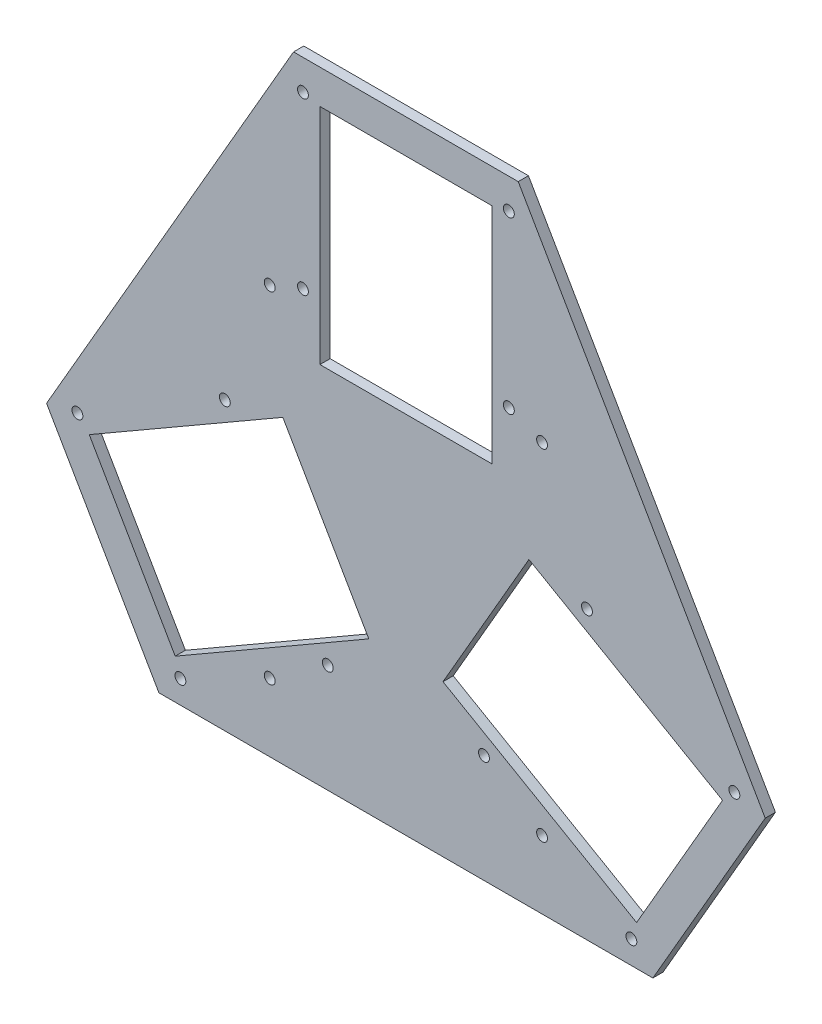
SolidWorks part; units mm, degrees
ref_plane "正面" through (0, 0, 0) normal (0, 0, 1) x (1, 0, 0)
ref_plane "平面" through (0, 0, 0) normal (0, 1, 0) x (1, 0, 0)
ref_plane "右側面" through (0, 0, 0) normal (1, 0, 0) x (0, 0, -1)
sketch "ｽｹｯﾁ1" plane through (0, 0, 0) normal (0, 0, 1) x (1, 0, 0)
  line L0 (0, -55) -> (0, 55) construction
  line L1 (-25.25, 92.8366) -> (25.25, 92.8366)
  line L2 (-25.25, 92.8366) -> (-25.25, 27.1634)
  line L3 (-25.25, 27.1634) -> (25.25, 27.1634) construction
  line L4 (25.25, 92.8366) -> (25.25, 27.1634)
  line L5 (-25.25, 92.8366) -> (25.25, 27.1634) construction
  line L6 (-25.25, 27.1634) -> (25.25, 92.8366) construction
  line L7 (0, 60) -> (0, 0) construction
  line L9 (30.25, 93.9588) -> (30.25, 43.9588) construction
  line L10 (-30.25, 93.9588) -> (-30.25, 43.9588) construction
  line L11 (93.0239, -24.5512) -> (67.7739, -68.2854)
  line L12 (93.0239, -24.5512) -> (36.1492, 8.2854)
  line L13 (67.7739, -68.2854) -> (10.8992, -35.4488)
  line L14 (36.1492, 8.2854) -> (10.8992, -35.4488) construction
  line L15 (93.0239, -24.5512) -> (10.8992, -35.4488) construction
  line L16 (36.1492, 8.2854) -> (67.7739, -68.2854) construction
  line L17 (51.9615, -30) -> (0, 0) construction
  line L18 (96.4957, -20.7821) -> (53.1944, 4.2179) construction
  line L19 (66.2457, -73.1767) -> (22.9444, -48.1767) construction
  line L20 (-67.7739, -68.2854) -> (-93.0239, -24.5512)
  line L21 (-67.7739, -68.2854) -> (-10.8992, -35.4488)
  line L22 (-93.0239, -24.5512) -> (-36.1492, 8.2854)
  line L23 (-10.8992, -35.4488) -> (-36.1492, 8.2854) construction
  line L24 (-67.7739, -68.2854) -> (-36.1492, 8.2854) construction
  line L25 (-10.8992, -35.4488) -> (-93.0239, -24.5512) construction
  line L26 (-51.9615, -30) -> (0, 0) construction
  line L27 (-66.2457, -73.1767) -> (-22.9444, -48.1767) construction
  line L28 (-96.4957, -20.7821) -> (-53.1944, 4.2179) construction
  line L29 (55, 0) -> (-55, 0) construction
  line L30 (-33.0033, 102.8366) -> (33.0033, 102.8366)
  line L31 (0, 160) -> (-138.5641, -80) construction
  line L32 (-138.5641, -80) -> (138.5641, -80) construction
  line L33 (138.5641, -80) -> (0, 160) construction
  line L34 (33.0033, 102.8366) -> (105.5608, -22.8366)
  line L35 (105.5608, -22.8366) -> (72.5575, -80)
  line L36 (72.5575, -80) -> (-72.5575, -80)
  line L37 (-72.5575, -80) -> (-105.5608, -22.8366)
  line L38 (-105.5608, -22.8366) -> (-33.0033, 102.8366)
  line L39 (-25.25, 27.1634) -> (25.25, 27.1634)
  line L40 (-40, -60) -> (40, -60) construction
  line L41 (-40, -60) -> (-40, 40) construction
  line L42 (-40, 40) -> (40, 40) construction
  line L43 (40, -60) -> (40, 40) construction
  line L44 (-40, -60) -> (40, 40) construction
  line L45 (-40, 40) -> (40, -60) construction
  line L46 (36.1492, 8.2854) -> (10.8992, -35.4488)
  line L47 (-10.8992, -35.4488) -> (-36.1492, 8.2854)
  circle A0 centre (30.25, 93.9588) radius 1.6
  circle A1 centre (30.25, 43.9588) radius 1.6
  circle A2 centre (-30.25, 43.9588) radius 1.6
  circle A3 centre (-30.25, 93.9588) radius 1.6
  circle A4 centre (66.2457, -73.1767) radius 1.6
  circle A5 centre (96.4957, -20.7821) radius 1.6
  circle A6 centre (53.1944, 4.2179) radius 1.6
  circle A7 centre (22.9444, -48.1767) radius 1.6
  circle A8 centre (-96.4957, -20.7821) radius 1.6
  circle A9 centre (-66.2457, -73.1767) radius 1.6
  circle A10 centre (-22.9444, -48.1767) radius 1.6
  circle A11 centre (-53.1944, 4.2179) radius 1.6
  circle A12 centre (0, 0) radius 80 construction
  circle A13 centre (-40, 40) radius 1.6
  circle A14 centre (40, 40) radius 1.6
  circle A15 centre (40, -60) radius 1.6
  circle A16 centre (-40, -60) radius 1.6
  point P0 (0, 60)
  point P19 (30.25, 68.9588)
  point P46 (0, 0)
  point P48 (0, -80)
  point P59 (0, -10)
  point P76 (0, 0)
  dimension "D1" = 3.2
  dimension "D12" = 3.2
  dimension "D2" = 50.5
  dimension "D3" = 65.6732
  dimension "D4" = 50
  dimension "D5" = 5
  dimension "D6" = 60
  dimension "D8" = 68.9588
  dimension "D9" = 80
  dimension "D10" = 10
  dimension "D11" = 10
  dimension "D13" = 100
  dimension "D14" = 80
  dimension "D15" = 0
  dimension "D7" = 3
  dimension "D16" = 3
extrude "ﾎﾞｽ - 押し出し1" add sketch "ｽｹｯﾁ1" along normal blind 3 contours L38 L37 L36 L35 L34 L30 A16 A15 A14 A13 A11 A9 A8 A7 A5 A4 A2 A1 A0 L47 L21 L20 L22 L46 L12 L11 L13 region at (0, 0.0184, 0)
equation "\"D3@ｽｹｯﾁ1\"=39/sin(40)+5"
equation "\"D8@ｽｹｯﾁ1\"=\"D6@ｽｹｯﾁ1\"+5/tan(40)+3"
